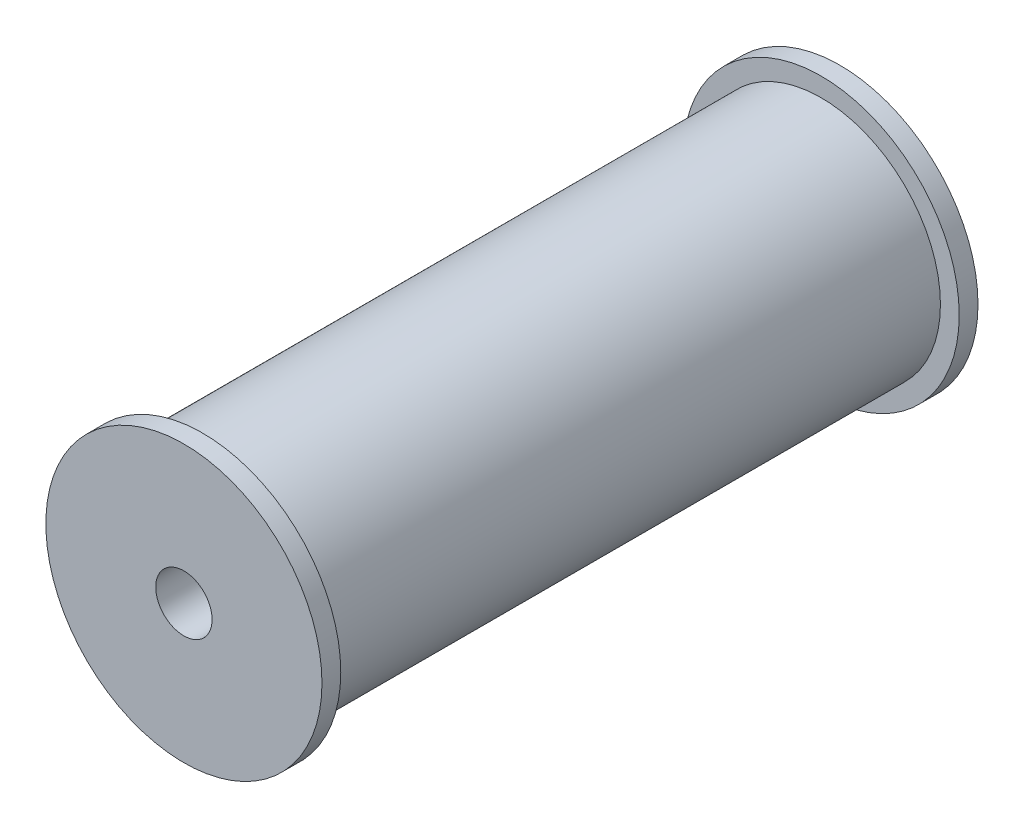
SolidWorks part; units mm, degrees
ref_plane "Front Plane" through (0, 0, 0) normal (0, 0, 1) x (1, 0, 0)
ref_plane "Top Plane" through (0, 0, 0) normal (0, 1, 0) x (1, 0, 0)
ref_plane "Right Plane" through (0, 0, 0) normal (1, 0, 0) x (0, 0, -1)
sketch "Sketch1" plane through (0, 0, 0) normal (0, 0, 1) x (1, 0, 0)
  circle A0 centre (0, 0) radius 12.7
  dimension "D1" = 25.4
extrude "Boss-Extrude1" add sketch "Sketch1" along normal blind 69.85
sketch "Sketch2" plane through (0, 0, 69.85) normal (0, 0, 1) x (1, 0, 0)
  circle A0 centre (0, 0) radius 3
  dimension "D1" = 6
extrude "Cut-Extrude3" cut sketch "Sketch2" against normal up to surface (69.85 mm away) up to face at (12.7, 0, 0)
sketch "Sketch3" plane through (0, 0, 0) normal (0, 0, 1) x (1, 0, 0)
  circle A0 centre (0, 0) radius 14.7
  circle A1 centre (0, 0) radius 3
extrude "Boss-Extrude2" add sketch "Sketch3" along normal blind 2
extrude "Boss-Extrude3" add sketch "Sketch3<2>" against normal blind 2 from surface starting at face at (3, 0, 69.85)
sketch "Sketch3<2>" plane through (0, 0, 0) normal (0, 0, 1) x (1, 0, 0) same geometry as "Sketch3"
